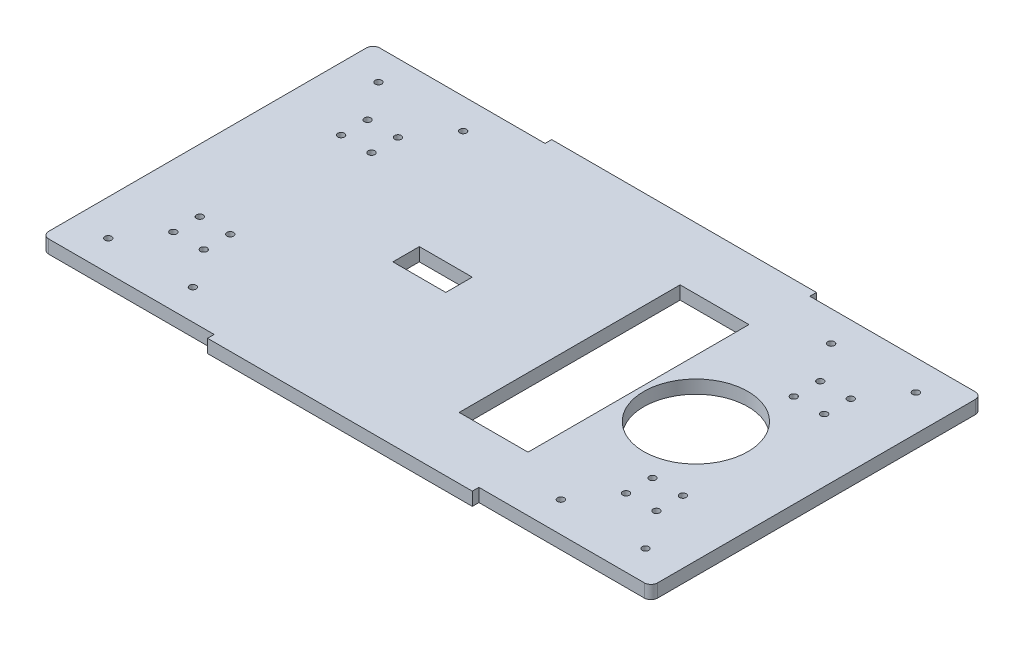
SolidWorks part; units mm, degrees
material "6061 Alloy"
ref_plane "Front" through (0, 0, 0) normal (0, 0, 1) x (1, 0, 0)
ref_plane "Top" through (0, 0, 0) normal (0, 1, 0) x (1, 0, 0)
ref_plane "Right" through (0, 0, 0) normal (1, 0, 0) x (0, 0, -1)
ref_plane "Plane1" through (0, 0, 0) normal (0, -1, 0) x (1, 0, 0)
sketch "Sketch1" plane through (0, 0, 0) normal (0, -1, 0) x (1, 0, 0)
  line L0 (142.875, 79.375) -> (66.817, 79.375)
  line L1 (63.642, 82.55) -> (63.642, 111.125)
  line L2 (60.467, 114.3) -> (-60.467, 114.3)
  line L3 (-63.642, 111.125) -> (-63.642, 82.55)
  line L4 (-66.817, 79.375) -> (-142.875, 79.375)
  line L5 (-146.05, 76.2) -> (-146.05, -76.2)
  line L6 (-142.875, -79.375) -> (-66.817, -79.375)
  line L7 (-63.642, -82.55) -> (-63.642, -111.125)
  line L8 (-60.467, -114.3) -> (60.467, -114.3)
  line L9 (63.642, -111.125) -> (63.642, -82.55)
  line L10 (66.817, -79.375) -> (142.875, -79.375)
  line L11 (146.05, -76.2) -> (146.05, 76.2)
  line L12 (0, -114.3) -> (0, 114.3) construction
  line L14 (-146.05, 0) -> (146.05, 0) construction
  arc A0 (146.05, 76.2) -> (142.875, 79.375) centre (142.875, 76.2) ccw
  arc A1 (66.817, 79.375) -> (63.642, 82.55) centre (66.817, 82.55) cw
  arc A2 (63.642, 111.125) -> (60.467, 114.3) centre (60.467, 111.125) ccw
  arc A3 (-60.467, 114.3) -> (-63.642, 111.125) centre (-60.467, 111.125) ccw
  arc A4 (-63.642, 82.55) -> (-66.817, 79.375) centre (-66.817, 82.55) cw
  arc A5 (-142.875, 79.375) -> (-146.05, 76.2) centre (-142.875, 76.2) ccw
  arc A6 (-146.05, -76.2) -> (-142.875, -79.375) centre (-142.875, -76.2) ccw
  arc A7 (-66.817, -79.375) -> (-63.642, -82.55) centre (-66.817, -82.55) cw
  arc A8 (-63.642, -111.125) -> (-60.467, -114.3) centre (-60.467, -111.125) ccw
  arc A9 (60.467, -114.3) -> (63.642, -111.125) centre (60.467, -111.125) ccw
  arc A10 (63.642, -82.55) -> (66.817, -79.375) centre (66.817, -82.55) cw
  arc A11 (142.875, -79.375) -> (146.05, -76.2) centre (142.875, -76.2) ccw
  point P38 (0, 0)
  point P39 (0, 0)
  dimension "D5" = 3.175
  dimension "D1" = 292.1
  dimension "D2" = 127.284
  dimension "D3" = 158.75
  dimension "D4" = 228.6
extrude "Boss-Extrude1" add sketch "Sketch1" against normal blind 6.35
sketch "Sketch2" plane through (0, 6.35, 0) normal (0, 1, 0) x (1, 0, 0)
  line L1 (-50.8, 6.35) -> (-25.4, 6.35)
  line L14 (-50.8, 6.35) -> (-50.8, -6.35)
  line L15 (-50.8, -6.35) -> (-25.4, -6.35)
  line L16 (-25.4, 6.35) -> (-25.4, -6.35)
  line L17 (-50.8, 6.35) -> (-25.4, -6.35) construction
  line L18 (-50.8, -6.35) -> (-25.4, 6.35) construction
  line L19 (146.05, 76.2) -> (146.05, -76.2) construction
  point P0 (-38.1, 0)
  dimension "D1" = 25.4
  dimension "D2" = 12.7
  dimension "D3" = 184.15
extrude "Cut-Extrude1" cut sketch "Sketch2" against normal through all contours L16 L1 L14 L15 region at (-38.1, 6.35, 0)
sketch "Sketch4" [suppressed] plane through (0, 6.35, 0) normal (0, 1, 0) x (1, 0, 0)
  line L0 (66.817, 82.55) -> (149.225, 82.55) construction
  line L1 (97.79, 82.55) -> (130.81, 82.55)
  line L2 (97.79, 82.55) -> (97.79, 63.73)
  line L3 (97.79, 63.73) -> (130.81, 63.73)
  line L4 (130.81, 82.55) -> (130.81, 63.73)
  line L5 (152.4, 79.375) -> (152.4, -79.375) construction
  line L6 (0, 0) -> (235.1316, 0) construction
  line L7 (0, 0) -> (0, 158.7845) construction
  line L8 (97.79, -63.73) -> (130.81, -63.73)
  line L9 (130.81, -82.55) -> (130.81, -63.73)
  line L10 (97.79, -82.55) -> (130.81, -82.55)
  line L11 (97.79, -82.55) -> (97.79, -63.73)
  line L12 (-97.79, -82.55) -> (-97.79, -63.73)
  line L13 (-97.79, -82.55) -> (-130.81, -82.55)
  line L14 (-130.81, -82.55) -> (-130.81, -63.73)
  line L15 (-97.79, -63.73) -> (-130.81, -63.73)
  line L16 (-97.79, 63.73) -> (-130.81, 63.73)
  line L17 (-130.81, 82.55) -> (-130.81, 63.73)
  line L18 (-97.79, 82.55) -> (-130.81, 82.55)
  line L19 (-97.79, 82.55) -> (-97.79, 63.73)
  dimension "D1" = 21.59
  dimension "D2" = 33.02
  dimension "D3" = 18.82
extrude "Cut-Extrude2" [suppressed] cut sketch "Sketch4" against normal blind 3.175
sketch "Sketch6" plane through (0, 0, 0) normal (0, -1, 0) x (1, 0, 0)
  line L0 (142.875, 79.375) -> (66.817, 79.375) construction
  line L1 (-101.6, 114.3) -> (101.6, 114.3)
  line L2 (-101.6, 114.3) -> (-101.6, 79.375)
  line L3 (-101.6, 79.375) -> (101.6, 79.375)
  line L4 (101.6, 114.3) -> (101.6, 79.375)
  line L5 (60.467, 114.3) -> (-60.467, 114.3) construction
  line L6 (0, 0) -> (0, 146.3522) construction
  line L7 (0, 0) -> (181.3201, 0) construction
  line L8 (-101.6, -79.375) -> (101.6, -79.375)
  line L9 (101.6, -114.3) -> (101.6, -79.375)
  line L10 (-101.6, -114.3) -> (101.6, -114.3)
  line L11 (-101.6, -114.3) -> (-101.6, -79.375)
  dimension "D1" = 203.2
extrude "Cut-Extrude3" cut sketch "Sketch6" against normal through all
sketch "Sketch9" plane through (0, 6.35, 0) normal (0, 1, 0) x (1, 0, 0)
  line L0 (0, 0) -> (199.3964, 0) construction
  line L1 (0, 0) -> (0, 106.1579) construction
  line L2 (-142.875, 79.375) -> (142.875, 79.375) construction
  line L3 (-63.5, 79.375) -> (63.5, 79.375)
  line L4 (-63.5, 79.375) -> (-63.5, 82.55)
  line L5 (-63.5, 82.55) -> (63.5, 82.55)
  line L6 (63.5, 79.375) -> (63.5, 82.55)
  line L7 (-63.5, -82.55) -> (63.5, -82.55)
  line L8 (63.5, -79.375) -> (63.5, -82.55)
  line L9 (-63.5, -79.375) -> (63.5, -79.375)
  line L10 (-63.5, -79.375) -> (-63.5, -82.55)
  dimension "D1" = 127
  dimension "D2" = 3.175
extrude "Boss-Extrude3" add sketch "Sketch9" against normal up to surface (6.35 mm away) up to face at (0, 0, 0)
ref_plane "Plane2" through (0, 0, -70.993) normal (0, 0, 1) x (1, 0, 0)
sketch "Sketch12" plane through (0, 0, 0) normal (0, -1, 0) x (1, 0, 0)
  line L0 (-146.05, 76.2) -> (-146.05, -76.2) construction
  line L1 (-63.5, 79.375) -> (-142.875, 79.375) construction
  circle A0 centre (-128.905, 64.825) radius 1.5875
  circle A1 centre (-88.265, 64.825) radius 1.5875
  circle A2 centre (-101.2892, 46.585) radius 1.5875
  circle A3 centre (-101.2892, 33.885) radius 1.5875
  circle A4 centre (-115.8808, 33.885) radius 1.5875
  circle A5 centre (-115.8808, 46.585) radius 1.5875
  dimension "D1" = 3.175
  dimension "D2" = 12.7
  dimension "D3" = 14.5915
  dimension "D4" = 30.1692
  dimension "D5" = 32.79
  dimension "D6" = 14.55
  dimension "D7" = 17.145
  dimension "D8" = 40.64
extrude "Cut-Extrude5" cut sketch "Sketch12" against normal through all and the other way through all
ref_plane "Plane3" through (0, 0, 0) normal (1, 0, 0) x (0, 0, -1)
ref_plane "Plane4" through (0, 0, 0) normal (0, 0, -1) x (-1, 0, 0)
mirror "Mirror1" about plane through (0, 0, 0) normal (1, 0, 0) of "Cut-Extrude5"
mirror "Mirror2" about plane through (0, 0, 0) normal (0, 0, -1) of "Mirror1"
sketch "Sketch13" plane through (0, 6.35, 0) normal (0, 1, 0) x (1, 0, 0)
  line L0 (3.4925, 0) -> (-3.4925, 0) construction
  line L1 (146.05, 76.2) -> (146.05, -76.2) construction
  line L2 (146.05, 0) -> (180.623, 0) construction
  circle A0 centre (88.2115, 0) radius 25
  dimension "D2" = 50
  dimension "D1" = 57.8385
extrude "Cut-Extrude6" cut sketch "Sketch13" against normal through all
sketch "Sketch14" plane through (0, 6.35, 0) normal (0, 1, 0) x (1, 0, 0)
  line L12 (-142.875, -79.375) -> (-63.5, -79.375)
  line L13 (-63.5, -79.375) -> (-63.5, -82.55)
  line L14 (-63.5, -82.55) -> (63.5, -82.55)
  line L15 (63.5, -82.55) -> (63.5, -79.375)
  line L16 (63.5, -79.375) -> (142.875, -79.375)
  line L17 (146.05, -76.2) -> (146.05, 76.2)
  line L18 (142.875, 79.375) -> (63.5, 79.375)
  line L19 (63.5, 79.375) -> (63.5, 82.55)
  line L20 (63.5, 82.55) -> (-63.5, 82.55)
  line L21 (-63.5, 82.55) -> (-63.5, 79.375)
  line L22 (-63.5, 79.375) -> (-142.875, 79.375)
  line L23 (-146.05, 76.2) -> (-146.05, -76.2)
  line L24 (-142.875, -79.375) -> (-63.5, -79.375)
  line L25 (-63.5, -79.375) -> (-63.5, -82.55)
  line L26 (-63.5, -82.55) -> (63.5, -82.55)
  line L27 (63.5, -82.55) -> (63.5, -79.375)
  line L28 (63.5, -79.375) -> (142.875, -79.375)
  line L29 (146.05, -76.2) -> (146.05, 76.2)
  line L30 (142.875, 79.375) -> (63.5, 79.375)
  line L31 (63.5, 79.375) -> (63.5, 82.55)
  line L32 (63.5, 82.55) -> (-63.5, 82.55)
  line L33 (-63.5, 82.55) -> (-63.5, 79.375)
  line L34 (-63.5, 79.375) -> (-142.875, 79.375)
  line L35 (-146.05, 76.2) -> (-146.05, -76.2)
  arc A4 (-146.05, -76.2) -> (-142.875, -79.375) centre (-142.875, -76.2) ccw
  arc A5 (142.875, -79.375) -> (146.05, -76.2) centre (142.875, -76.2) ccw
  arc A6 (146.05, 76.2) -> (142.875, 79.375) centre (142.875, 76.2) ccw
  arc A7 (-142.875, 79.375) -> (-146.05, 76.2) centre (-142.875, 76.2) ccw
  arc A8 (-146.05, -76.2) -> (-142.875, -79.375) centre (-142.875, -76.2) ccw
  arc A9 (142.875, -79.375) -> (146.05, -76.2) centre (142.875, -76.2) ccw
  arc A10 (146.05, 76.2) -> (142.875, 79.375) centre (142.875, 76.2) ccw
  arc A11 (-142.875, 79.375) -> (-146.05, 76.2) centre (-142.875, 76.2) ccw
  dimension "D1" = 0
sketch "Sketch15" plane through (0, 6.35, 0) normal (0, 1, 0) x (1, 0, 0)
  line L0 (60.673, -53) -> (60.673, 53)
  line L1 (60.673, 53) -> (27.653, 53)
  line L2 (27.653, 53) -> (27.653, -53)
  line L3 (27.653, -53) -> (60.673, -53)
  line L7 (0, 0) -> (165.7309, 0) construction
  point P9 (63.213, 0)
  dimension "D1" = 33.02
  dimension "D2" = 106
  dimension "D3" = 2.54
extrude "Cut-Extrude7" cut sketch "Sketch15" against normal through all
equation "\"0.125inin\"=0.1"
